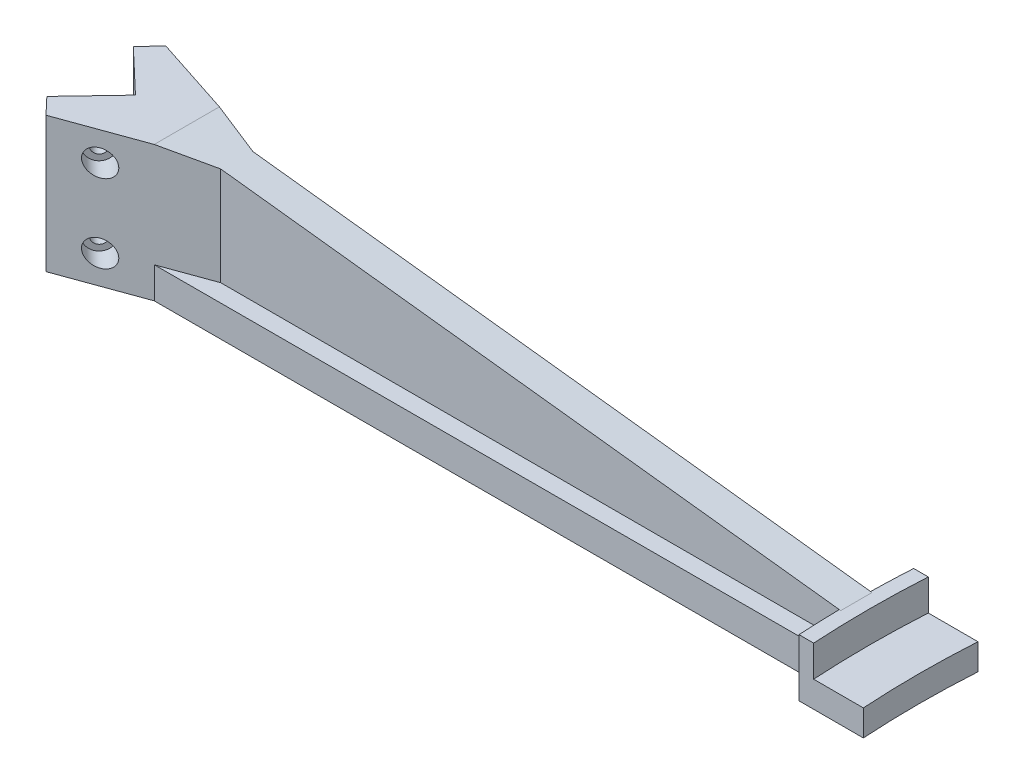
SolidWorks part; units mm, degrees
ref_plane "Front Plane" through (0, 0, 0) normal (0, 0, 1) x (1, 0, 0)
ref_plane "Top Plane" through (0, 0, 0) normal (0, 1, 0) x (1, 0, 0)
ref_plane "Right Plane" through (0, 0, 0) normal (1, 0, 0) x (0, 0, -1)
sketch "Sketch2" plane through (0, 0, 0) normal (0, 1, 0) x (1, 0, 0)
  line L0 (0, 0) -> (-276.0246, 0) construction
  line L1 (0, 0) -> (135.9511, 0) construction
  line L2 (-276.0246, 0) -> (-292.5966, 15.7434)
  line L3 (-292.5966, 15.7434) -> (-286.5108, 22.1496)
  line L4 (-286.5108, 22.1496) -> (-276.0246, 12.1877)
  line L5 (-276.0246, 12.1877) -> (-276.0246, 0)
  line L14 (0.6536, 22) -> (25.3402, 22)
  line L15 (0.6536, -22) -> (25.3402, -22)
  line L16 (25.3402, 22) -> (25.3402, -22) construction
  line L34 (-276.0246, 0) -> (-292.5966, -17.4443)
  line L49 (-292.5966, -17.4443) -> (-286.5108, -23.8504)
  line L50 (-286.5108, -23.8504) -> (-276.0246, -12.8123)
  line L51 (-276.0246, -12.8123) -> (-276.0246, 0)
  line L52 (-276.0246, 12.1877) -> (0.2109, 12.5)
  line L53 (-276.0246, -12.8123) -> (0.2109, -12.5)
  line L54 (0.2109, -12.5) -> (0.2109, 12.5) construction
  line L55 (-276.0246, 12.1877) -> (-276.0246, 24.2548) construction
  line L56 (-276.0246, -12.8123) -> (-276.0246, -19.1381)
  line L58 (-286.5108, 22.1496) -> (-256.0246, 12.2103)
  line L62 (-286.5108, -23.8504) -> (-256.0246, -12.7897)
  line L63 (-256.0246, 12.2103) -> (-256.0246, -12.7897)
  line L64 (-256.0246, -12.7897) -> (-219.7315, 0.3778)
  line L65 (-256.0246, 12.2103) -> (-219.7315, 0.3778)
  arc A0 (0.6536, 22) -> (0.6536, -22) centre (370.6, 0) ccw
  arc A1 (6.2636, 22) -> (6.2636, -22) centre (370.6, 0) ccw
  arc A2 (25.3402, 22) -> (25.3402, -22) centre (370.6, 0) ccw
  point P32 (5.6, 0)
  dimension "D2" = 365
  dimension "D3" = 5.6
  dimension "D4" = 19.04
  dimension "D7" = 25
  dimension "D5" = 133.531
  dimension "D6" = 136.469
  dimension "D8" = 25
  dimension "D9" = 44
  dimension "D10" = 20
  dimension "D18" = 46
  dimension "D19" = 281.6246
extrude "Boss-Extrude2" add sketch "Sketch2" against normal blind 12 contours A0 L52 L53 | L53 L52 | L53 | L52 | A1 L14 A0 L15 | L50 L51 L34 L49 | L5 L4 L3 L2 | L65 L63 L64 region at (-282.9032, 0, -12.1717) region at (-282.9032, 0, 13.1665) region at (-266.0246, 0, 0.301) region at (-272.8533, 0, -15.5159) region at (-272.8533, 0, 16.4841) region at (-243.9269, 0, 0.0672) region at (-119.1345, 0, 0.1509) region at (3.0196, 0, 0)
extrude "Boss-Extrude3" add sketch "Sketch2<5>" along normal blind 10 from surface contours A2 L14 A1 L15 region at (15.3473, 0, 0) starting at face at (-148.6736, -12, 0.3062)
sketch "Sketch2<5>" plane through (0, 0, 0) normal (0, 1, 0) x (1, 0, 0) same geometry as "Sketch2"
extrude "Boss-Extrude4" add sketch "Sketch2<6>" along normal blind 22 from surface contours A1 L14 A0 L15 region at (3.0196, 0, 0) starting at face at (-145.7416, -12, 0.3062)
sketch "Sketch2<6>" plane through (0, 0, 0) normal (0, 1, 0) x (1, 0, 0) same geometry as "Sketch2"
extrude "Boss-Extrude7" add sketch "Sketch2<9>" along normal blind 40 contours L63 L52 L5 L51 L53 | L5 L4 L3 L2 | L58 L4 L52 | L50 L51 L34 L49 | L50 L62 L53 | L65 L63 L64 region at (-282.9032, 0, -12.1717) region at (-282.9032, 0, 13.1665) region at (-266.0246, 0, 0.301) region at (-272.8533, 0, -15.5159) region at (-272.8533, 0, 16.4841) region at (-243.9269, 0, 0.0672)
sketch "Sketch2<9>" plane through (0, 0, 0) normal (0, 1, 0) x (1, 0, 0) same geometry as "Sketch2"
sketch "Sketch4" plane through (0, 0, 0) normal (0, 0, 1) x (1, 0, 0)
  line L2 (-292.5966, -12) -> (-292.5966, 40) construction
  line L5 (0.6536, 10) -> (-256.0246, 40)
  line L6 (-286.5108, 40) -> (-219.7315, 40) construction
  line L8 (-276.0246, 0) -> (0.2109, 0) construction
  line L9 (-256.0246, 0) -> (0.6536, 0)
  line L10 (0.6536, 0) -> (0.6536, 10)
  line L11 (0.6536, -12) -> (0.6536, 10) construction
  line L12 (0.6536, 10) -> (0, 10) construction
  line L13 (-256.0246, 40) -> (-256.0246, 0)
  dimension "D1" = 36.572
extrude "Boss-Extrude17" add sketch "Sketch4" along normal blind 6 and the other way blind 6
sketch "Sketch5" plane through (0, 0, 0) normal (0, 0, 1) x (1, 0, 0)
  line L0 (0.6536, 10) -> (-256.0246, 40) construction
  line L1 (0.6536, 10) -> (-256.0246, 40)
extrude "Cut-Extrude-Thin1" cut sketch "Sketch5" against normal through all and the other way through all thin contours L1 thin type one direction wall 10
sketch "Sketch6" plane through (-145.0852, 0, -137.8309) normal (-0.725, 0, -0.6887) x (-0.6887, 0, 0.725)
  line L0 (200.1118, 29) -> (200.1118, -1) construction
  line L1 (190.1118, 40) -> (214.1728, 40) construction
  line L2 (190.1118, 40) -> (210.1118, 40)
  line L3 (190.1118, 40) -> (190.1118, -12)
  line L4 (190.1118, -12) -> (210.1118, -12)
  line L5 (210.1118, 40) -> (210.1118, -12)
  line L6 (190.1118, 40) -> (210.1118, -12) construction
  line L7 (190.1118, -12) -> (210.1118, 40) construction
  line L8 (190.1118, -12) -> (190.1118, 40) construction
  line L9 (190.1118, -12) -> (214.1728, -12) construction
  circle A0 centre (200.1118, 29) radius 5
  circle A1 centre (200.1118, -1) radius 5
  circle A2 centre (200.1118, 29) radius 2.75
  circle A3 centre (200.1118, -1) radius 2.75
  point P3 (200.1118, 14)
  point P6 (200.1118, 14)
  dimension "D2" = 10
  dimension "D3" = 5.5
  dimension "D1" = 20
  dimension "D4" = 30
extrude "Cut-Extrude1" cut sketch "Sketch6" against normal through all from offset 8 contours A0 | A1 offset against normal yes
extrude "Cut-Extrude2" cut sketch "Sketch6<4>" against normal through all both and the other way through all contours A2 | A3
sketch "Sketch6<4>" plane through (-145.0852, 0, -137.8309) normal (-0.725, 0, -0.6887) x (-0.6887, 0, 0.725) same geometry as "Sketch6"
mirror "Mirror1" about plane through (0, 0, 0) normal (0, 0, 1) of "Cut-Extrude1", "Cut-Extrude2"
